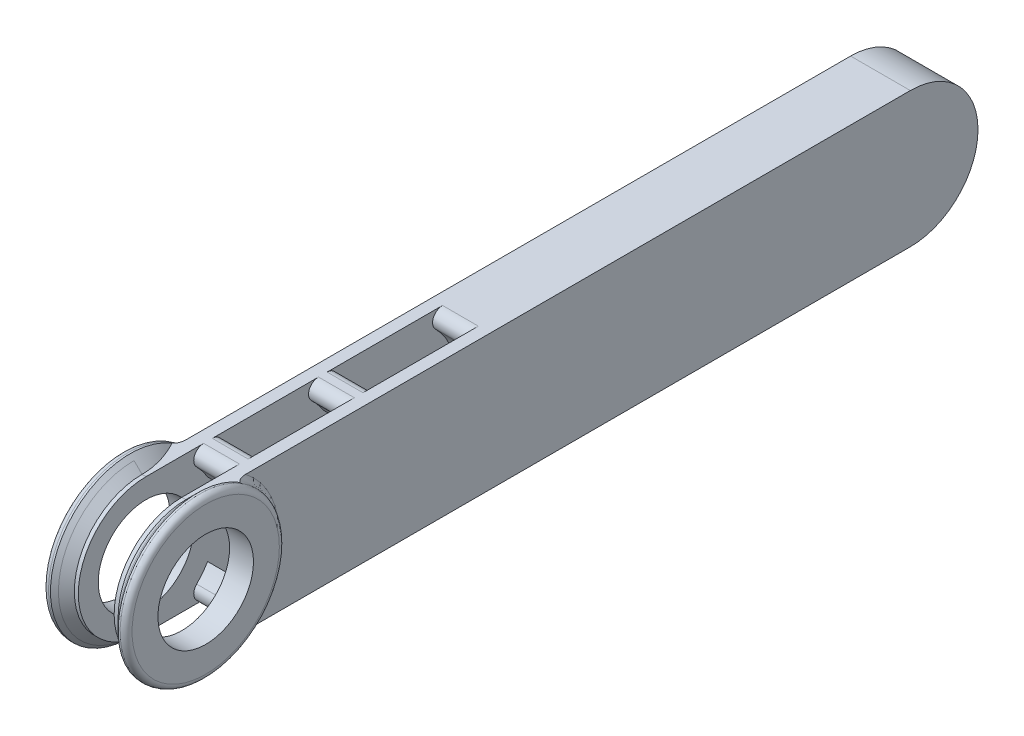
SolidWorks part; units mm, degrees
ref_plane "Front Plane" through (0, 0, 0) normal (0, 0, 1) x (1, 0, 0)
ref_plane "Top Plane" through (0, 0, 0) normal (0, 1, 0) x (1, 0, 0)
ref_plane "Right Plane" through (0, 0, 0) normal (1, 0, 0) x (0, 0, -1)
sketch "Sketch1" plane through (0, 0, 0) normal (1, 0, 0) x (0, 0, -1)
  line L0 (-45, 0) -> (45, 0) construction
  line L1 (-45, 8.5) -> (45, 8.5)
  line L2 (-45, -8.5) -> (45, -8.5)
  arc A0 (-45, 8.5) -> (-45, -8.5) centre (-45, 0) ccw
  arc A1 (45, -8.5) -> (45, 8.5) centre (45, 0) ccw
  circle A2 centre (-45, 0) radius 6
  point P3 (0, 0)
  point P10 (-49.1483, 0)
  dimension "D1" = 12
  dimension "D2" = 8.5
  dimension "D3" = 90
extrude "Boss-Extrude1" add sketch "Sketch1" along normal mid plane 7.5
sketch "Sketch2" plane through (0, 0, 0) normal (1, 0, 0) x (0, 0, -1)
  line L0 (-45, 0) -> (-30, 0) construction
  line L1 (-30, 0) -> (-15, 0) construction
  arc A0 (-37.2653, 4.6016) -> (-37.2653, -4.6016) centre (-45, 0) ccw
  arc A1 (-37.2653, -4.6016) -> (-22.7347, -4.6016) centre (-30, 0) ccw
  arc A2 (-22.7347, -4.6016) -> (-22.7347, 4.6016) centre (-15, 0) ccw
  arc A3 (-22.7347, 4.6016) -> (-37.2653, 4.6016) centre (-30, 0) ccw
  dimension "D1" = 18
  dimension "D3" = 8.6
  dimension "D2" = 15
extrude "Cut-Extrude1" cut sketch "Sketch2" against normal mid plane 4.5
sketch "Sketch3" plane through (3.75, 0, 0) normal (1, 0, 0) x (0, 0, -1)
  circle A0 centre (-45, 0) radius 6
  circle A1 centre (-45, 0) radius 10
  circle A2 centre (-45, 0) radius 6 construction
  dimension "D1" = 20
extrude "Boss-Extrude2" add sketch "Sketch3" along normal blind 1.5
mirror "Mirror1" about plane through (0, 0, 0) normal (1, 0, 0) of "Boss-Extrude2"
chamfer "Chamfer1" distance 0.5 angle 45 2 edges at (-3.75, 0, 55) (3.75, 0, 55)
fillet "Fillet4" radius 0.75 2 edges at (-5.25, 0, 35) (5.25, 0, 35)
fillet "Fillet3" radius 0.7 2 edges at (-3.75, 0, 35) (3.75, 0, 35)
fillet "Fillet2" radius 1.25 10 edges at (0, -8.5, 42.042) (0, 8.5, 42.042) (0, -8.5, 31.3077) (0, -8.5, 28.6923) (0, -8.5, 17.958) (0, -8.5, 12.042) (0, 8.5, 12.042) (0, 8.5, 17.958) (0, 8.5, 28.6923) (0, 8.5, 31.3077)
chamfer "Chamfer2" distance 1 angle 45 6 edges at (3.75, 8.5, 42.8787) (3.75, -8.5, 42.8787) (3.75, 0, 53.5) (-3.75, 8.5, 42.8787) (-3.75, -8.5, 42.8787) (-3.75, 0, 53.5)
